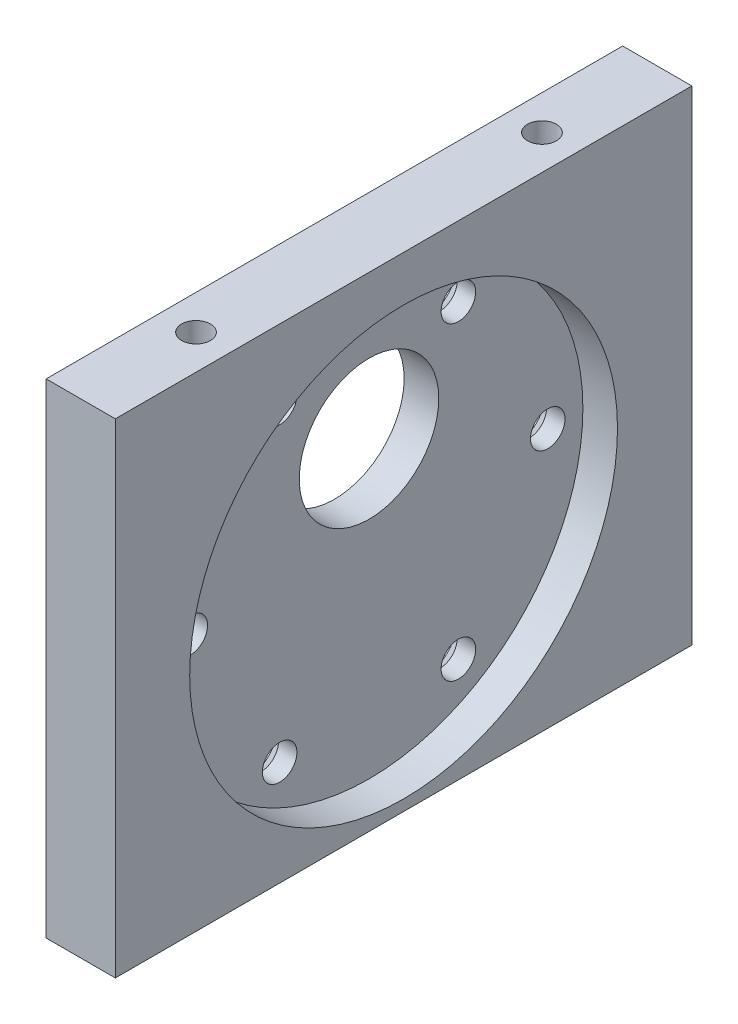
SolidWorks part; units mm, degrees
material "1060 Alloy"
ref_plane "Front Plane" through (0, 0, 0) normal (0, 0, 1) x (1, 0, 0)
ref_plane "Top Plane" through (0, 0, 0) normal (0, 1, 0) x (1, 0, 0)
ref_plane "Right Plane" through (0, 0, 0) normal (1, 0, 0) x (0, 0, -1)
sketch "Sketch1" plane through (0, 0, 0) normal (0, 1, 0) x (1, 0, 0)
  line L1 (0, 0) -> (6, 0)
  line L2 (0, 0) -> (0, 50)
  line L3 (0, 50) -> (6, 50)
  line L4 (6, 0) -> (6, 50)
  dimension "D1" = 50
  dimension "D2" = 6
extrude "Boss-Extrude1" add sketch "Sketch1" along normal blind 42
hole_wizard "Tap Drill for M3 Tap1" positions "Sketch3" profile "Sketch2" hole size "M3" standard "ISO"
sketch "Sketch3" plane through (0, 42, 0) normal (0, 1, 0) x (-1, 0, 0)
  line L0 (0, 0) -> (-6, 0) construction
  line L1 (-6, 0) -> (-6, -50) construction
  line L2 (-6, -50) -> (0, -50) construction
  point P0 (-3, -10)
  point P1 (-3, -40)
  point P6 (-3, -50)
  dimension "D1" = 10
  dimension "D2" = 3
  dimension "D3" = 10
sketch "Sketch2" plane through (3, 42, -10) normal (1, 0, 0) x (0, 0, 1)
  line L0 (0, 0) -> (0, 10.7511)
  line L1 (0, 10.7511) -> (1.25, 10)
  line L2 (1.25, 10) -> (1.25, 0)
  line L5 (1.25, 0) -> (0, 0)
  line L10 (0, 10.7511) -> (-1.25, 10) construction
  line L11 (0, -6.35) -> (0, 107.95) construction
  dimension "Hole Dia." = 2.5
  dimension "Hole Depth" = 10
  dimension "Drill Angle" = 118
hole_wizard "Tap Drill for M3 Tap2" positions "Sketch5" profile "Sketch4" hole size "M3" standard "ISO"
sketch "Sketch5" plane through (0, 0, 0) normal (0, -1, 0) x (1, 0, 0)
  line L0 (6, 0) -> (6, -50) construction
  line L1 (0, 0) -> (6, 0) construction
  line L2 (6, -50) -> (0, -50) construction
  point P0 (3, -10)
  point P1 (3, -40)
  dimension "D1" = 3
  dimension "D2" = 10
  dimension "D3" = 10
sketch "Sketch4" plane through (3, 0, -10) normal (1, 0, 0) x (0, 0, -1)
  line L0 (0, 0) -> (0, 7.7511)
  line L1 (0, 7.7511) -> (1.25, 7)
  line L2 (1.25, 7) -> (1.25, 0)
  line L5 (1.25, 0) -> (0, 0)
  line L10 (0, 7.7511) -> (-1.25, 7) construction
  line L11 (0, -6.35) -> (0, 107.95) construction
  dimension "Hole Dia." = 2.5
  dimension "Hole Depth" = 7
  dimension "Drill Angle" = 118
sketch "Sketch6" plane through (6, 0, 0) normal (1, 0, 0) x (0, 0, -1)
  line L0 (0, 42) -> (0, 0) construction
  line L1 (0, 0) -> (50, 0) construction
  circle A0 centre (25, 19.5) radius 18.55
  dimension "D2" = 37.1
  dimension "D1" = 25
  dimension "D3" = 19.5
extrude "Cut-Extrude1" cut sketch "Sketch6" against normal blind 3
sketch "Sketch7" plane through (3, 0, 0) normal (1, 0, 0) x (0, 0, -1)
  line L1 (6.45, 19.5) -> (25, 19.5) construction
  circle A0 centre (25, 26.5) radius 6.05
  circle A1 centre (25, 19.5) radius 18.55 construction
  circle A3 centre (9.5, 19.5) radius 1.5
  circle A4 centre (25, 19.5) radius 18.55 construction
  dimension "D1" = 12.1
  dimension "D4" = 3
  dimension "D2" = 25
  dimension "D3" = 7
  dimension "D5" = 15.5
extrude "Cut-Extrude2" cut sketch "Sketch7" against normal up to next
pattern_circular "CirPattern1" count 6 over 360 about axis through (6, 19.5, -25) along (1, 0, 0) of face at (3, 19.5, -11)
chamfer "Chamfer1" distance 1.4 angle 45 6 edges at (0, 19.5, -39) (0, 7.3756, -32) (0, 7.3756, -18) (0, 19.5, -11) (0, 31.6244, -18) (0, 31.6244, -32)
